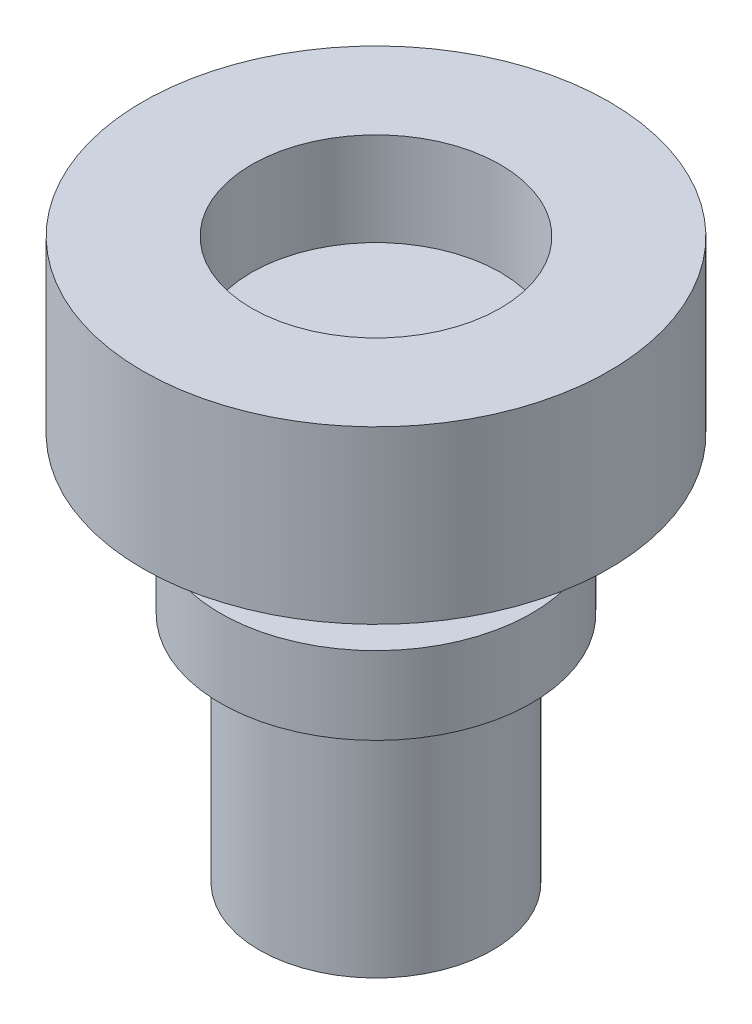
SolidWorks part; units mm, degrees
ref_plane "Front Plane" through (0, 0, 0) normal (0, 0, 1) x (1, 0, 0)
ref_plane "Top Plane" through (0, 0, 0) normal (0, 1, 0) x (1, 0, 0)
ref_plane "Right Plane" through (0, 0, 0) normal (1, 0, 0) x (0, 0, -1)
sketch "Sketch1" plane through (0, 0, 0) normal (0, 1, 0) x (1, 0, 0)
  circle A0 centre (-0.522, 0.5111) radius 1.6
  circle A1 centre (-0.522, 0.5111) radius 3
  dimension "D1" = 3.2
  dimension "D2" = 6
extrude "Boss-Extrude1" add sketch "Sketch1" along normal blind 2.2
extrude "Boss-Extrude2" add sketch "Sketch1<3>" along normal blind 1 contours A0 region at (-0.522, 0, -0.5111)
sketch "Sketch1<3>" plane through (0, 0, 0) normal (0, 1, 0) x (1, 0, 0) same geometry as "Sketch1"
sketch "Sketch5" plane through (0, 0, 0) normal (0, -1, 0) x (1, 0, 0)
  circle A2 centre (-0.522, -0.5111) radius 1.5
  circle A3 centre (-0.522, -0.5111) radius 1.5
  dimension "D2" = 3
  dimension "D1" = 1.5
extrude "Boss-Extrude3" add sketch "Sketch5" along normal blind 1 contours A3
sketch "Sketch6" plane through (0, -1, 0) normal (0, -1, 0) x (1, 0, 0)
  circle A0 centre (-0.522, -0.5111) radius 2
  dimension "D1" = 4
extrude "Boss-Extrude4" add sketch "Sketch6" along normal blind 1
sketch "Sketch8" plane through (0, -2, 0) normal (0, -1, 0) x (-1, 0, 0)
  circle A0 centre (0.522, 0.5111) radius 1.5
  dimension "D1" = 3
extrude "Boss-Extrude5" add sketch "Sketch8" along normal blind 3 contours A0
